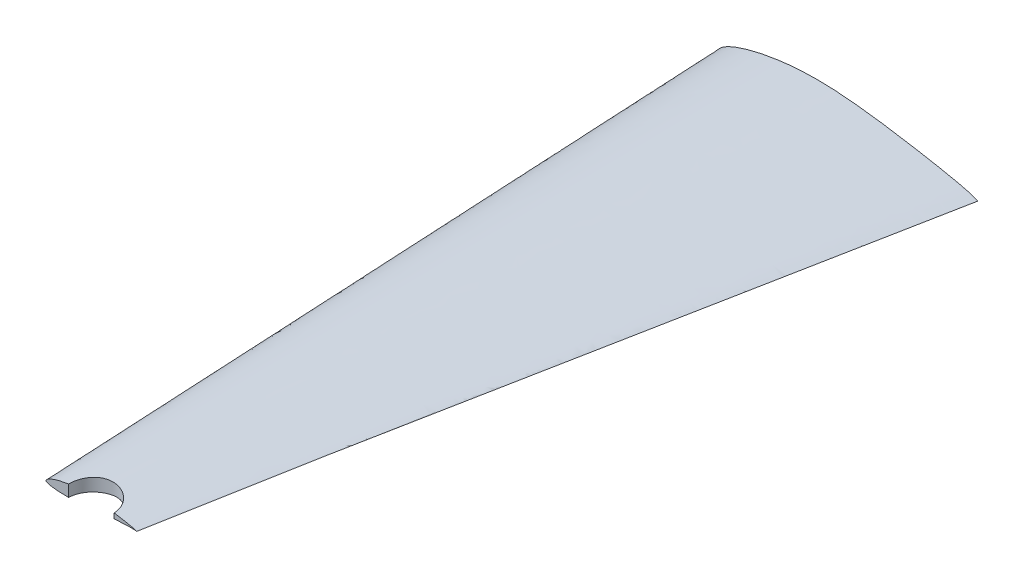
SolidWorks part; units mm, degrees
ref_plane "Front Plane" through (0, 0, 0) normal (0, 0, 1) x (1, 0, 0)
ref_plane "Top Plane" through (0, 0, 0) normal (0, 1, 0) x (1, 0, 0)
ref_plane "Right Plane" through (0, 0, 0) normal (1, 0, 0) x (0, 0, -1)
curve "Curve1"
  spline degree 3 poles (0.9921, 0.0008, 0) (1.0019, -0.0008, 0) (0.9929, 0.0016, 0) (0.9861, 0.0043, 0) (0.9706, 0.0096, 0) (0.9519, 0.0152, 0) (0.9278, 0.021, 0) (0.8992, 0.0273, 0) (0.8662, 0.0341, 0) (0.8293, 0.0413, 0) (0.789, 0.0488, 0) (0.746, 0.0564, 0) (0.7007, 0.0641, 0) (0.6538, 0.0714, 0) (0.6058, 0.0784, 0) (0.5573, 0.0846, 0) (0.5088, 0.0898, 0) (0.4609, 0.0938, 0) (0.4138, 0.0961, 0) (0.3679, 0.0966, 0) (0.3232, 0.0952, 0) (0.2801, 0.092, 0) (0.2388, 0.0874, 0) (0.1997, 0.0815, 0) (0.1631, 0.0746, 0) (0.1296, 0.0669, 0) (0.0993, 0.0585, 0) (0.0726, 0.0496, 0) (0.0499, 0.0404, 0) (0.0312, 0.031, 0) (0.0168, 0.0217, 0) (0.0085, 0.0145, 0) (0.0039, 0.009, 0) (0.0018, 0.0058, 0) (0.0004, 0.0024, 0) (0, 0.0003, 0) (0, -0.0012, 0) (0.0006, -0.0026, 0) (0.002, -0.0043, 0) (0.0049, -0.007, 0) (0.0107, -0.0108, 0) (0.0215, -0.0156, 0) (0.0378, -0.0206, 0) (0.0598, -0.0253, 0) (0.0864, -0.0294, 0) (0.1174, -0.033, 0) (0.1523, -0.036, 0) (0.1908, -0.0383, 0) (0.2323, -0.0397, 0) (0.2764, -0.0402, 0) (0.3228, -0.0395, 0) (0.3711, -0.0373, 0) (0.4212, -0.0335, 0) (0.4729, -0.0284, 0) (0.526, -0.0227, 0) (0.5798, -0.0169, 0) (0.6336, -0.0114, 0) (0.6866, -0.0064, 0) (0.7378, -0.0023, 0) (0.7866, 0.0009, 0) (0.832, 0.0031, 0) (0.8733, 0.0042, 0) (0.9096, 0.0045, 0) (0.9406, 0.0038, 0) (0.9645, 0.0029, 0) (0.984, 0.0013, 0) (0.9921, 0.0008, 0) (1.0019, -0.0008, 0) (0.9929, 0.0016, 0) knots -0.016161 -0.007282 -0.001839 0 0.00178 0.006777 0.014308 0.024046 0.036116 0.050547 0.06713 0.085624 0.105767 0.127282 0.149864 0.17323 0.197069 0.221103 0.245052 0.268663 0.291773 0.314299 0.336178 0.357377 0.377792 0.397225 0.415489 0.432417 0.447849 0.461651 0.473687 0.483898 0.492263 0.498797 0.499955 0.502811 0.504371 0.50536 0.505925 0.506503 0.507535 0.509205 0.512345 0.517665 0.526422 0.537425 0.550643 0.565966 0.583206 0.602155 0.622587 0.644255 0.666998 0.690703 0.715307 0.740824 0.767084 0.793717 0.820331 0.846519 0.871863 0.895937 0.918335 0.938667 0.956573 0.971715 0.983839 0.992718 0.998161 1 1.00178 1.006777 1.014308 periodic
sketch "Sketch1" plane through (0, 0, 0) normal (0, 0, 1) x (1, 0, 0)
  line L0 (1122.2059, -30.8288) -> (-1162.7941, -35.0845) construction
  spline S1 degree 3 poles (1104.1363, -28.0222) (1126.6295, -31.7875) (1105.8826, -26.3024) (1090.4575, -20.1288) (1054.9513, -7.9956) (1012.296, 4.6638) (957.0478, 17.8508) (891.7164, 32.0367) (816.2153, 47.3864) (731.9108, 63.6705) (639.9041, 80.612) (541.5101, 97.9168) (438.0076, 115.0958) (330.7593, 131.7488) (221.0675, 147.3336) (110.2357, 161.251) (-0.493, 172.9975) (-110.0556, 181.8587) (-217.6516, 186.9061) (-322.6724, 187.859) (-424.6755, 184.4831) (-523.1626, 176.9995) (-617.5035, 166.1709) (-706.8843, 152.6667) (-790.3524, 136.737) (-867.0563, 118.889) (-936.2082, 99.5088) (-997.0691, 79.0242) (-1049.0447, 57.9028) (-1091.6336, 36.4479) (-1124.4686, 15.1943) (-1143.3869, -1.4067) (-1153.8659, -14.0298) (-1158.6984, -21.3016) (-1161.9612, -29.0988) (-1162.8988, -33.8887) (-1162.7223, -37.2464) (-1161.3764, -40.4052) (-1158.2301, -44.4654) (-1151.5185, -50.6376) (-1138.2079, -59.2164) (-1113.635, -70.0567) (-1076.2399, -81.3981) (-1026.0446, -92.1031) (-965.2298, -101.4019) (-894.4776, -109.4657) (-814.6314, -116.0953) (-726.7099, -121.1028) (-631.8133, -124.2931) (-530.9633, -125.2112) (-425.0342, -123.2363) (-314.6436, -117.9744) (-200.1569, -109.1265) (-81.9663, -97.1903) (39.2548, -83.9633) (162.1641, -70.4688) (285.0306, -57.6215) (406.0083, -46.0046) (523.1884, -36.2734) (634.6311, -28.7415) (738.3789, -23.5277) (832.7109, -20.7776) (915.5317, -20.0924) (986.36, -21.3847) (1040.9806, -23.338) (1085.6437, -26.9173) (1104.1363, -28.0222) (1126.6295, -31.7875) (1105.8826, -26.3024) knots -0.016161 -0.007282 -0.001839 0 0.00178 0.006777 0.014308 0.024046 0.036116 0.050547 0.06713 0.085624 0.105767 0.127282 0.149864 0.17323 0.197069 0.221103 0.245052 0.268663 0.291773 0.314299 0.336178 0.357377 0.377792 0.397225 0.415489 0.432417 0.447849 0.461651 0.473687 0.483898 0.492263 0.498797 0.499955 0.502811 0.504371 0.50536 0.505925 0.506503 0.507535 0.509205 0.512345 0.517665 0.526422 0.537425 0.550643 0.565966 0.583206 0.602155 0.622587 0.644255 0.666998 0.690703 0.715307 0.740824 0.767084 0.793717 0.820331 0.846519 0.871863 0.895937 0.918335 0.938667 0.956573 0.971715 0.983839 0.992718 0.998161 1 1.00178 1.006777 1.014308 only from (1122.2059, -30.8288) to (1122.2059, -30.8288)
  dimension "D1" = 2285
ref_plane "Plane1" through (0, 0, 6200) normal (0, 0, 1) x (1, 0, 0)
ref_plane "Plane3" through (0, -35.0845, 0) normal (0, 1, 0) x (1, 0, 0)
sketch "Sketch4" plane through (0, -35.0845, 0) normal (0, 1, 0) x (1, 0, 0)
  line L1 (1122.2059, 0) -> (-1162.7941, 0) construction
  line L2 (-172.1886, -6200) -> (172.1886, -6200) construction
  line L4 (-1162.7941, 0) -> (-862.7941, -6200)
sketch "Sketch5" plane through (0, 0, 6200) normal (0, 0, 1) x (1, 0, 0)
  line L0 (-62.749, -35.2354) -> (-862.7688, -35.3009) construction
  spline S1 degree 3 poles (-69.0897, -34.3504) (-61.22, -35.5469) (-68.4893, -33.741) (-73.9048, -31.6671) (-86.3598, -27.6181) (-101.3126, -23.4229) (-120.663, -19.1093) (-143.5377, -14.4998) (-169.9677, -9.5373) (-199.4749, -4.2947) (-231.6736, 1.1372) (-266.1033, 6.6624) (-302.3153, 12.1171) (-339.8318, 17.3686) (-378.1955, 22.2345) (-416.9483, 26.5125) (-455.6538, 30.0335) (-493.9373, 32.5536) (-531.5145, 33.7529) (-568.1715, 33.5367) (-603.7528, 31.8256) (-638.0855, 28.6992) (-670.9538, 24.4271) (-702.0769, 19.2472) (-731.124, 13.2516) (-757.8002, 6.6219) (-781.8329, -0.5031) (-802.9662, -7.9701) (-820.9952, -15.6131) (-835.7466, -23.3233) (-847.0949, -30.9123) (-853.6106, -36.8049) (-857.2018, -41.2651) (-858.8503, -43.8282) (-859.9483, -46.5664) (-860.2505, -48.243) (-860.1714, -49.4139) (-859.6851, -50.5093) (-858.5659, -51.9099) (-856.1913, -54.0289) (-851.5011, -56.9533) (-842.8685, -60.6082) (-829.7584, -64.3709) (-812.1844, -67.8447) (-790.9116, -70.7722) (-766.1771, -73.2167) (-738.2762, -75.1133) (-707.5656, -76.4015) (-674.4302, -77.0191) (-639.2289, -76.8125) (-602.2702, -75.5698) (-563.7715, -73.1566) (-523.8621, -69.4706) (-482.6761, -64.6873) (-440.4393, -59.4377) (-397.6147, -54.086) (-354.8016, -48.9603) (-312.6413, -44.2739) (-271.7964, -40.2655) (-232.9425, -37.0546) (-196.7619, -34.6929) (-163.8546, -33.2402) (-134.9538, -32.5684) (-110.2281, -32.6493) (-91.1554, -33.0456) (-75.5494, -34.0614) (-69.0897, -34.3504) (-61.22, -35.5469) (-68.4893, -33.741) knots -0.016161 -0.007282 -0.001839 0 0.00178 0.006777 0.014308 0.024046 0.036116 0.050547 0.06713 0.085624 0.105767 0.127282 0.149864 0.17323 0.197069 0.221103 0.245052 0.268663 0.291773 0.314299 0.336178 0.357377 0.377792 0.397225 0.415489 0.432417 0.447849 0.461651 0.473687 0.483898 0.492263 0.498797 0.499955 0.502811 0.504371 0.50536 0.505925 0.506503 0.507535 0.509205 0.512345 0.517665 0.526422 0.537425 0.550643 0.565966 0.583206 0.602155 0.622587 0.644255 0.666998 0.690703 0.715307 0.740824 0.767084 0.793717 0.820331 0.846519 0.871863 0.895937 0.918335 0.938667 0.956573 0.971715 0.983839 0.992718 0.998161 1 1.00178 1.006777 1.014308 only from (-62.7688, -35.2354) to (-62.7688, -35.2354)
  dimension "D1" = 800
sketch "Sketch6" plane through (0, 0, 6200) normal (0, 0, 1) x (1, 0, 0)
  line L0 (-862.7688, -35.3009) -> (-860.1517, -49.246)
  spline S0 degree 3 poles (-69.0897, -34.3504) (-61.22, -35.5469) (-68.4893, -33.741) (-73.9048, -31.6671) (-86.3598, -27.6181) (-101.3126, -23.4229) (-120.663, -19.1093) (-143.5377, -14.4998) (-169.9677, -9.5373) (-199.4749, -4.2947) (-231.6736, 1.1372) (-266.1033, 6.6624) (-302.3153, 12.1171) (-339.8318, 17.3686) (-378.1955, 22.2345) (-416.9483, 26.5125) (-455.6538, 30.0335) (-493.9373, 32.5536) (-531.5145, 33.7529) (-568.1715, 33.5367) (-603.7528, 31.8256) (-638.0855, 28.6992) (-670.9538, 24.4271) (-702.0769, 19.2472) (-731.124, 13.2516) (-757.8002, 6.6219) (-781.8329, -0.5031) (-802.9662, -7.9701) (-820.9952, -15.6131) (-835.7466, -23.3233) (-847.0949, -30.9123) (-853.6106, -36.8049) (-857.2018, -41.2651) (-858.8503, -43.8282) (-859.9483, -46.5664) (-860.2505, -48.243) (-860.1714, -49.4139) (-859.6851, -50.5093) (-858.5659, -51.9099) (-856.1913, -54.0289) (-851.5011, -56.9533) (-842.8685, -60.6082) (-829.7584, -64.3709) (-812.1844, -67.8447) (-790.9116, -70.7722) (-766.1771, -73.2167) (-738.2762, -75.1133) (-707.5656, -76.4015) (-674.4302, -77.0191) (-639.2289, -76.8125) (-602.2702, -75.5698) (-563.7715, -73.1566) (-523.8621, -69.4706) (-482.6761, -64.6873) (-440.4393, -59.4377) (-397.6147, -54.086) (-354.8016, -48.9603) (-312.6413, -44.2739) (-271.7964, -40.2655) (-232.9425, -37.0546) (-196.7619, -34.6929) (-163.8546, -33.2402) (-134.9538, -32.5684) (-110.2281, -32.6493) (-91.1554, -33.0456) (-75.5494, -34.0614) (-69.0897, -34.3504) (-61.22, -35.5469) (-68.4893, -33.741) knots -0.016161 -0.007282 -0.001839 0 0.00178 0.006777 0.014308 0.024046 0.036116 0.050547 0.06713 0.085624 0.105767 0.127282 0.149864 0.17323 0.197069 0.221103 0.245052 0.268663 0.291773 0.314299 0.336178 0.357377 0.377792 0.397225 0.415489 0.432417 0.447849 0.461651 0.473687 0.483898 0.492263 0.498797 0.499955 0.502811 0.504371 0.50536 0.505925 0.506503 0.507535 0.509205 0.512345 0.517665 0.526422 0.537425 0.550643 0.565966 0.583206 0.602155 0.622587 0.644255 0.666998 0.690703 0.715307 0.740824 0.767084 0.793717 0.820331 0.846519 0.871863 0.895937 0.918335 0.938667 0.956573 0.971715 0.983839 0.992718 0.998161 1 1.00178 1.006777 1.014308 only from (-62.7688, -35.2354) to (-62.7688, -35.2354) construction
ref_axis "Axis2" through (-860.1517, -49.246, 6200) along (-0.0488, 0.0023, -0.9988)
loft "Loft5" add profiles "Sketch1", "Sketch5" connector at (-829.2128, 127.5517, 0) connector at (-729.5824, 13.4038, 6200)
sketch "Sketch9" plane through (0, 0, 0) normal (0, 0, -1) x (-1, 0, 0)
  line L1 (513.5943, 97.9459) -> (666.6195, 97.9459)
  line L2 (513.5943, 97.9459) -> (513.5943, -16.278)
  line L3 (513.5943, -16.278) -> (666.6195, -16.278)
  line L4 (666.6195, 97.9459) -> (666.6195, -16.278)
  line L5 (513.5943, 97.9459) -> (666.6195, -16.278) construction
  line L6 (513.5943, -16.278) -> (666.6195, 97.9459) construction
  point P0 (590.1069, 40.8339)
extrude "Boss-Extrude1" add sketch "Sketch9" along normal blind 30
extrude "Cut-Extrude3" cut sketch "Sketch13" along normal blind 9300
sketch "Sketch13" plane through (-2172.4747, -6356.5137, -7372.8161) normal (0, 1, 0) x (1, 0, 0)
  circle A0 centre (1710.9861, -13572.8161) radius 200
ref_plane "Plane4" through (0, 0, 600) normal (0, 0, -1) x (-1, 0, 0)
sketch "Sketch14" plane through (0, 0, 600) normal (0, 0, -1) x (-1, 0, 0)
  point P0 (474.2063, 51.3807)
